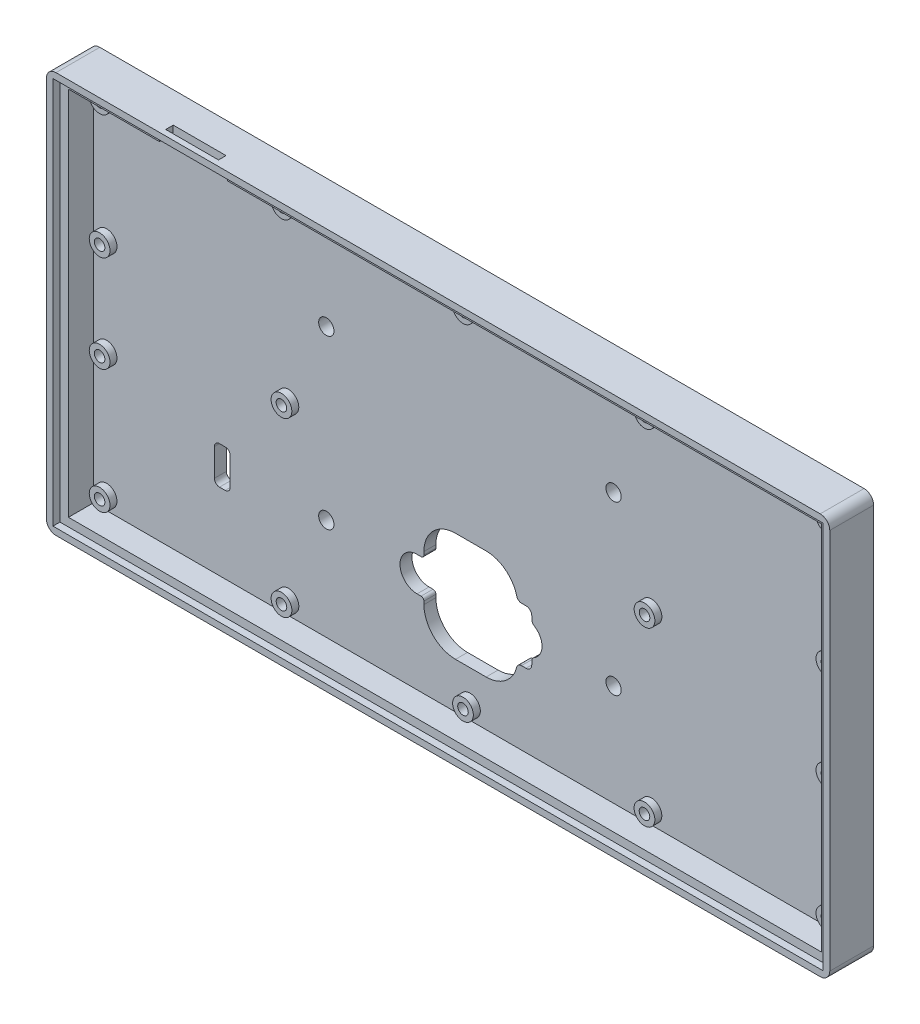
SolidWorks part; units mm, degrees
ref_plane "Front Plane" through (0, 0, 0) normal (0, 0, 1) x (1, 0, 0)
ref_plane "Top Plane" through (0, 0, 0) normal (0, 1, 0) x (1, 0, 0)
ref_plane "Right Plane" through (0, 0, 0) normal (1, 0, 0) x (0, 0, -1)
sketch "PCB" plane through (0, 0, 0) normal (0, 0, 1) x (1, 0, 0)
  line L0 (96.2635, 45.5524) -> (101.8921, 45.5524) construction
  line L1 (-101.8921, 51.181) -> (101.8921, 51.181) construction
  line L2 (-101.8921, 51.181) -> (-101.8921, -51.181) construction
  line L3 (-101.8921, -51.181) -> (101.8921, -51.181) construction
  line L4 (101.8921, 51.181) -> (101.8921, -51.181) construction
  line L5 (-101.8921, 51.181) -> (101.8921, -51.181) construction
  line L6 (-101.8921, -51.181) -> (101.8921, 51.181) construction
  line L7 (96.2635, 45.5524) -> (96.2635, 51.181) construction
  line L8 (-96.2635, 45.5524) -> (-101.8921, 45.5524) construction
  line L9 (-96.2635, -45.5524) -> (-96.2635, -51.181) construction
  line L10 (-92.8243, 0) -> (-92.8243, 25.6794) construction
  line L11 (-98.8568, 31.7119) -> (-86.7918, 31.7119)
  line L12 (-98.8568, 31.7119) -> (-98.8568, 19.6469)
  line L13 (-98.8568, 19.6469) -> (-86.7918, 19.6469)
  line L14 (-86.7918, 31.7119) -> (-86.7918, 19.6469)
  line L15 (-98.8568, 31.7119) -> (-86.7918, 19.6469) construction
  line L16 (-98.8568, 19.6469) -> (-86.7918, 31.7119) construction
  line L17 (-98.8568, 6.0325) -> (-86.7918, 6.0325)
  line L18 (-98.8568, 6.0325) -> (-98.8568, -6.0325)
  line L19 (-98.8568, -6.0325) -> (-86.7918, -6.0325)
  line L20 (-86.7918, 6.0325) -> (-86.7918, -6.0325)
  line L21 (-98.8568, 6.0325) -> (-86.7918, -6.0325) construction
  line L22 (-98.8568, -6.0325) -> (-86.7918, 6.0325) construction
  line L23 (-98.8568, -19.6469) -> (-86.7918, -19.6469)
  line L24 (-98.8568, -19.6469) -> (-98.8568, -31.7119)
  line L25 (-98.8568, -31.7119) -> (-86.7918, -31.7119)
  line L26 (-86.7918, -19.6469) -> (-86.7918, -31.7119)
  line L27 (-98.8568, -19.6469) -> (-86.7918, -31.7119) construction
  line L28 (-98.8568, -31.7119) -> (-86.7918, -19.6469) construction
  line L29 (86.7918, 31.7119) -> (98.8568, 31.7119)
  line L30 (86.7918, 31.7119) -> (86.7918, 19.6469)
  line L31 (86.7918, 19.6469) -> (98.8568, 19.6469)
  line L32 (98.8568, 31.7119) -> (98.8568, 19.6469)
  line L33 (86.7918, 31.7119) -> (98.8568, 19.6469) construction
  line L34 (86.7918, 19.6469) -> (98.8568, 31.7119) construction
  line L35 (86.7918, 6.0325) -> (98.8568, 6.0325)
  line L36 (86.7918, 6.0325) -> (86.7918, -6.0325)
  line L37 (86.7918, -6.0325) -> (98.8568, -6.0325)
  line L38 (98.8568, 6.0325) -> (98.8568, -6.0325)
  line L39 (86.7918, 6.0325) -> (98.8568, -6.0325) construction
  line L40 (86.7918, -6.0325) -> (98.8568, 6.0325) construction
  line L41 (86.7918, -19.6469) -> (98.8568, -19.6469)
  line L42 (86.7918, -19.6469) -> (86.7918, -31.7119)
  line L43 (86.7918, -31.7119) -> (98.8568, -31.7119)
  line L44 (98.8568, -19.6469) -> (98.8568, -31.7119)
  line L45 (86.7918, -19.6469) -> (98.8568, -31.7119) construction
  line L46 (86.7918, -31.7119) -> (98.8568, -19.6469) construction
  line L47 (-92.8243, 0) -> (-92.8243, -25.6794) construction
  line L48 (-92.8243, 25.6794) -> (-101.8921, 25.6794) construction
  line L49 (92.8243, 25.6794) -> (101.8921, 25.6794) construction
  line L50 (-3.114, -17.4711) -> (-3.114, -27.7327) construction
  circle A0 centre (-96.2635, 45.5524) radius 0.9995
  circle A1 centre (-96.2635, -45.5524) radius 0.9995
  circle A2 centre (96.2635, -45.5524) radius 0.9995
  circle A3 centre (96.2635, 45.5524) radius 0.9995
  circle A4 centre (-3.114, -17.4711) radius 1.9939
  circle A5 centre (-3.114, -27.7327) radius 1.9939
  point P0 (0, 0)
  point P14 (-92.8243, 25.6794)
  point P23 (-92.8243, 0)
  point P28 (-92.8243, -25.6794)
  point P33 (92.8243, 25.6794)
  point P38 (92.8243, 0)
  point P43 (92.8243, -25.6794)
  point P54 (0.1092, -22.6019)
  point P55 (-7.5006, -22.6019)
  point P60 (-3.114, -22.6019)
  dimension "D4" = 1.999
  dimension "D14" = 3.9878
  dimension "D1" = 203.7842
  dimension "D2" = 102.362
  dimension "D3" = 5.6286
  dimension "D5" = 25.5016
  dimension "D6" = 25.5016
  dimension "D7" = 9.0678
  dimension "D8" = 12.065
  dimension "D9" = 102.0013
  dimension "D10" = 28.5791
  dimension "D11" = 7.6098
  dimension "D12" = 5.1308
  dimension "D13" = 3.2233
sketch "DT_plug" plane through (0, 0, 0) normal (0, 0, 1) x (1, 0, 0)
  line L0 (29.2774, -40.0231) -> (29.2774, -5.0981) construction
  dimension "D1" = 34.925
sketch "display_screen" plane through (0, 0, 0) normal (0, 0, 1) x (1, 0, 0)
  line L1 (-80.3275, 46.3296) -> (83.7565, 46.3296) construction
  line L2 (-80.3275, 46.3296) -> (-80.3275, -50.9016) construction
  line L3 (-80.3275, -50.9016) -> (83.7565, -50.9016) construction
  line L4 (83.7565, 46.3296) -> (83.7565, -50.9016) construction
  line L5 (-78.2955, 44.2976) -> (78.2955, 44.2976) construction
  line L6 (-78.2955, 44.2976) -> (-78.2955, -44.2976) construction
  line L7 (-78.2955, -44.2976) -> (78.2955, -44.2976) construction
  line L8 (78.2955, 44.2976) -> (78.2955, -44.2976) construction
  point P8 (0, 44.2976)
  point P10 (-78.2955, 0)
  dimension "D1" = 164.084
  dimension "D2" = 97.2312
  dimension "D3" = 6.604
  dimension "D4" = 2.032
  dimension "D5" = 2.032
  dimension "D6" = 5.461
ref_plane "back_of_PCB" through (0, 0, -1.8542) normal (0, 0, 1) x (1, 0, 0)
ref_plane "back_PCB_clearance" through (0, 0, -8.4582) normal (0, 0, 1) x (1, 0, 0)
sketch "Sketch4" plane through (0, 0, 0) normal (0, 0, 1) x (1, 0, 0)
  line L0 (-102.1461, 51.4096) -> (-102.1461, 53.1596) construction
  line L1 (-102.1461, 51.4096) -> (102.1461, 51.4096)
  line L2 (-102.1461, 51.4096) -> (-102.1461, -51.4096)
  line L3 (-102.1461, -51.4096) -> (102.1461, -51.4096)
  line L4 (102.1461, 51.4096) -> (102.1461, -51.4096)
  line L5 (-103.8961, 53.1596) -> (103.8961, 53.1596)
  line L6 (-103.8961, 53.1596) -> (-103.8961, -53.1596)
  line L7 (-103.8961, -53.1596) -> (103.8961, -53.1596)
  line L8 (103.8961, 53.1596) -> (103.8961, -53.1596)
  line L9 (-102.1461, 51.4096) -> (-103.8961, 51.4096) construction
  line L10 (102.1461, -51.4096) -> (102.1461, -53.1596) construction
  line L11 (102.1461, -51.4096) -> (103.8961, -51.4096) construction
  line L12 (-101.8921, 51.181) -> (101.8921, 51.181) construction
  line L13 (-101.8921, 51.181) -> (-101.8921, -51.181) construction
  line L14 (101.8921, 51.181) -> (101.8921, -51.181) construction
  line L15 (-101.8921, -51.181) -> (101.8921, -51.181) construction
  dimension "D1" = 1.75
  dimension "D2" = 0.2286
  dimension "D3" = 0.254
  dimension "D4" = 0.254
  dimension "D5" = 0.2286
extrude "Boss-Extrude1" add sketch "Sketch4" against normal up to surface (1.8542 mm away) up to plane "back_of_PCB"
sketch "Sketch5" plane through (0, 0, -1.8542) normal (0, 0, -1) x (-1, 0, 0)
  line L1 (-103.8961, 53.1596) -> (103.8961, 53.1596)
  line L2 (-103.8961, 53.1596) -> (-103.8961, -53.1596)
  line L3 (-103.8961, -53.1596) -> (103.8961, -53.1596)
  line L4 (103.8961, 53.1596) -> (103.8961, -53.1596)
  line L6 (101.8921, 51.181) -> (-101.8921, 51.181) construction
  line L7 (-99.8931, 49.182) -> (99.8931, 49.182)
  line L8 (-99.8931, 49.182) -> (-99.8931, -49.182)
  line L9 (-99.8931, -49.182) -> (99.8931, -49.182)
  line L10 (99.8931, 49.182) -> (99.8931, -49.182)
  line L11 (-99.8931, 49.182) -> (-99.8931, 51.181) construction
  line L12 (-99.8931, 49.182) -> (-101.8921, 49.182) construction
  line L13 (-101.8921, 51.181) -> (-101.8921, -51.181) construction
  line L14 (99.8931, -49.182) -> (101.8921, -49.182) construction
  line L15 (101.8921, 51.181) -> (101.8921, -51.181) construction
  line L16 (99.8931, -49.182) -> (99.8931, -51.181) construction
  line L17 (101.8921, -51.181) -> (-101.8921, -51.181) construction
  dimension "D1" = 1.999
extrude "Boss-Extrude2" add sketch "Sketch5" along normal up to surface (6.604 mm away) up to plane "back_PCB_clearance"
sketch "Sketch6" plane through (0, 0, -8.4582) normal (0, 0, -1) x (-1, 0, 0)
  line L0 (11.7018, -27.8978) -> (11.7018, -28.6979) construction
  line L1 (-103.8961, 53.1596) -> (103.8961, 53.1596)
  line L2 (-103.8961, 53.1596) -> (-103.8961, -53.1596)
  line L3 (-103.8961, -53.1596) -> (103.8961, -53.1596)
  line L4 (103.8961, 53.1596) -> (103.8961, -53.1596)
  line L5 (3.8278, -8.6319) -> (-4.2865, -8.6319) construction
  line L6 (11.7018, -16.5059) -> (11.7018, -17.306) construction
  line L7 (3.8278, -36.5719) -> (-4.2865, -36.5719) construction
  line L11 (12.9718, -18.576) -> (14.0259, -18.576) construction
  line L13 (12.9718, -26.6278) -> (14.0259, -26.6278) construction
  line L15 (-13.6655, -15.9344) -> (-14.8666, -15.9344) construction
  line L16 (-15.8826, -27.4219) -> (-15.8826, -28.2534) construction
  line L17 (-13.6655, -29.2694) -> (-14.8666, -29.2694) construction
  line L18 (-15.8826, -16.9504) -> (-15.8826, -17.782) construction
  line L20 (12.2098, -27.8978) -> (12.2098, -28.6979)
  line L21 (3.8278, -37.0799) -> (-4.2865, -37.0799)
  line L22 (-13.6655, -29.7774) -> (-14.8666, -29.7774)
  line L23 (-16.3906, -27.4219) -> (-16.3906, -28.2534)
  line L24 (-16.3906, -16.9504) -> (-16.3906, -17.782)
  line L25 (-13.6655, -15.4264) -> (-14.8666, -15.4264)
  line L26 (3.8278, -8.1239) -> (-4.2865, -8.1239)
  line L27 (12.2098, -16.5059) -> (12.2098, -17.306)
  line L28 (12.9718, -18.068) -> (14.0259, -18.068)
  line L29 (12.9718, -27.1358) -> (14.0259, -27.1358)
  arc A0 (-16.7989, -19.407) -> (-16.7989, -25.7969) centre (-14.8666, -22.6019) ccw construction
  arc A1 (12.9718, -18.576) -> (11.7018, -17.306) centre (12.9718, -17.306) cw construction
  arc A2 (12.9718, -26.6278) -> (11.7018, -27.8978) centre (12.9718, -27.8978) ccw construction
  arc A3 (14.0259, -26.6278) -> (14.0259, -18.576) centre (14.0259, -22.6019) ccw construction
  arc A4 (11.7018, -28.6979) -> (3.8278, -36.5719) centre (3.8278, -28.6979) cw construction
  arc A5 (11.7018, -16.5059) -> (3.8278, -8.6319) centre (3.8278, -16.5059) ccw construction
  arc A6 (-4.2865, -8.6319) -> (-11.9202, -14.5755) centre (-4.2865, -16.5059) ccw construction
  arc A7 (-11.9202, -14.5755) -> (-13.6655, -15.9344) centre (-13.6655, -14.1342) cw construction
  arc A8 (-4.2865, -36.5719) -> (-11.9202, -30.6283) centre (-4.2865, -28.6979) cw construction
  arc A9 (-11.9202, -30.6283) -> (-13.6655, -29.2694) centre (-13.6655, -31.0697) ccw construction
  arc A10 (-14.8666, -15.9344) -> (-15.8826, -16.9504) centre (-14.8666, -16.9504) ccw construction
  arc A11 (-15.8826, -17.782) -> (-16.7989, -19.407) centre (-17.7817, -17.782) cw construction
  arc A12 (-15.8826, -27.4219) -> (-16.7989, -25.7969) centre (-17.7817, -27.4219) ccw construction
  arc A13 (-15.8826, -28.2534) -> (-14.8666, -29.2694) centre (-14.8666, -28.2534) ccw construction
  arc A14 (12.2098, -28.6979) -> (3.8278, -37.0799) centre (3.8278, -28.6979) cw
  arc A15 (-4.2865, -37.0799) -> (-12.4127, -30.7529) centre (-4.2865, -28.6979) cw
  arc A16 (-12.4127, -30.7529) -> (-13.6655, -29.7774) centre (-13.6655, -31.0697) ccw
  arc A17 (-16.3906, -28.2534) -> (-14.8666, -29.7774) centre (-14.8666, -28.2534) ccw
  arc A18 (-16.3906, -27.4219) -> (-17.0618, -26.2315) centre (-17.7817, -27.4219) ccw
  arc A19 (-17.0618, -18.9723) -> (-17.0618, -26.2315) centre (-14.8666, -22.6019) ccw
  arc A20 (-16.3906, -17.782) -> (-17.0618, -18.9723) centre (-17.7817, -17.782) cw
  arc A21 (-14.8666, -15.4264) -> (-16.3906, -16.9504) centre (-14.8666, -16.9504) ccw
  arc A22 (-12.4127, -14.451) -> (-13.6655, -15.4264) centre (-13.6655, -14.1342) cw
  arc A23 (-4.2865, -8.1239) -> (-12.4127, -14.451) centre (-4.2865, -16.5059) ccw
  arc A24 (12.2098, -16.5059) -> (3.8278, -8.1239) centre (3.8278, -16.5059) ccw
  arc A25 (12.9718, -18.068) -> (12.2098, -17.306) centre (12.9718, -17.306) cw
  arc A26 (14.0259, -27.1358) -> (14.0259, -18.068) centre (14.0259, -22.6019) ccw
  arc A27 (12.9718, -27.1358) -> (12.2098, -27.8978) centre (12.9718, -27.8978) ccw
  point P6 (-0.1092, -22.6019)
  dimension "D7" = 3.7338
  dimension "D9" = 1.27
  dimension "D3" = 1.0541
  dimension "D10" = 7.874
  dimension "D13" = 1.8002
  dimension "D16" = 1.016
  dimension "D17" = 1.8991
  dimension "D2" = 11.811
  dimension "D4" = 13.97
  dimension "D5" = 15.7734
  dimension "D6" = 6.6675
  dimension "D8" = 1.016
  dimension "D11" = 0.8001
  dimension "D12" = 13.97
  dimension "D14" = 8.1143
  dimension "D15" = 6.6675
  dimension "D22" = 0.508
extrude "Boss-Extrude3" add sketch "Sketch6" along normal blind 3.175
sketch "Sketch10" plane through (0, 0, -11.6332) normal (0, 0, -1) x (-1, 0, 0)
  line L0 (-38.1, 22.225) -> (38.1, 22.225) construction
  line L1 (38.1, 22.225) -> (38.1, -22.225) construction
  line L3 (38.1, 22.225) -> (38.1, 53.1596) construction
  line L4 (-103.8961, 53.1596) -> (103.8961, 53.1596) construction
  line L5 (38.1, -22.225) -> (38.1, -53.1596) construction
  line L6 (103.8961, -53.1596) -> (-103.8961, -53.1596) construction
  circle A0 centre (-38.1, 22.225) radius 2.032
  circle A1 centre (-38.1, 22.225) radius 5.207 construction
  circle A2 centre (-38.1, -22.225) radius 5.207 construction
  circle A3 centre (-38.1, -22.225) radius 2.032
  circle A4 centre (38.1, -22.225) radius 2.032
  circle A5 centre (38.1, -22.225) radius 5.207 construction
  circle A6 centre (38.1, 22.225) radius 2.032
  circle A7 centre (38.1, 22.225) radius 5.207 construction
  point P12 (0, 22.225)
  dimension "D1" = 4.064
  dimension "D2" = 3.175
  dimension "D3" = 76.2
  dimension "D4" = 44.45
extrude "Cut-Extrude1" cut sketch "Sketch10" against normal up to next
fillet "Fillet1" radius 2.54 4 edges at (103.8961, 53.1596, -5.8166) (103.8961, -53.1596, -5.8166) (-103.8961, -53.1596, -5.8166) (-103.8961, 53.1596, -5.8166)
sketch "Sketch11" plane through (0, 0, -8.4582) normal (0, 0, 1) x (1, 0, 0)
  line L0 (-96.3835, 45.671) -> (-96.3835, 51.4096) construction
  line L1 (-96.3835, 45.671) -> (96.3835, 45.671) construction
  line L2 (-96.3835, 45.671) -> (-96.3835, -45.671) construction
  line L3 (-96.3835, -45.671) -> (96.3835, -45.671) construction
  line L4 (96.3835, 45.671) -> (96.3835, -45.671) construction
  line L5 (-102.1461, 51.4096) -> (102.1461, 51.4096) construction
  line L6 (-96.3835, 45.671) -> (-102.1461, 45.671) construction
  line L7 (-102.1461, 51.4096) -> (-102.1461, -51.4096) construction
  line L8 (96.3835, -45.671) -> (102.1461, -45.671) construction
  line L9 (102.1461, -51.4096) -> (102.1461, 51.4096) construction
  line L10 (96.3835, -45.671) -> (96.3835, -51.4096) construction
  line L11 (102.1461, -51.4096) -> (-102.1461, -51.4096) construction
  circle A0 centre (-96.3835, 45.671) radius 1.4
  circle A1 centre (0, 45.671) radius 1.4
  circle A2 centre (96.3835, 45.671) radius 1.4
  circle A3 centre (-96.3835, -45.671) radius 1.4
  circle A4 centre (96.3835, -45.671) radius 1.4
  circle A5 centre (96.3835, -12.808) radius 1.4
  circle A6 centre (96.3835, 12.808) radius 1.4
  circle A7 centre (0, -45.671) radius 1.4
  circle A8 centre (-96.3835, -12.808) radius 1.4
  circle A9 centre (-96.3835, 12.808) radius 1.4
  circle A10 centre (-48.1435, 45.671) radius 1.4
  circle A11 centre (48.1435, 45.671) radius 1.4
  circle A12 centre (48.1435, -45.671) radius 1.4
  circle A13 centre (-48.1435, -45.671) radius 1.4
  circle A14 centre (-48.1545, 0.033) radius 1.4
  circle A15 centre (48.1545, 0.033) radius 1.4
  dimension "D3" = 2.8
  dimension "D1" = 91.342
  dimension "D2" = 192.767
  dimension "D4" = 48.24
  dimension "D5" = 48.24
  dimension "D6" = 32.863
  dimension "D7" = 32.863
  dimension "D8" = 48.229
  dimension "D9" = 45.638
  dimension "D10" = 48.229
  dimension "D11" = 45.638
extrude "Cut-Extrude2" cut sketch "Sketch11" against normal up to next
sketch "Sketch12" plane through (0, 53.1596, 0) normal (0, 1, 0) x (1, 0, 0)
  line L0 (101.3561, 0) -> (-101.3561, 0) construction
  line L1 (-73.7461, 3.5) -> (-59.7461, 3.5)
  line L2 (-73.7461, 3.5) -> (-73.7461, 1.5)
  line L3 (-73.7461, 1.5) -> (-59.7461, 1.5)
  line L4 (-59.7461, 3.5) -> (-59.7461, 1.5)
  line L6 (-103.8961, 0) -> (-103.8961, 11.6332) construction
  dimension "D1" = 1.5
  dimension "D2" = 14
  dimension "D3" = 30.15
  dimension "D4" = 2
extrude "Cut-Extrude3" cut sketch "Sketch12" against normal up to next
sketch "Sketch13" plane through (0, 0, -1.8542) normal (0, 0, 1) x (1, 0, 0)
  line L0 (-59.7461, 51.4096) -> (102.1461, 51.4096) construction
  line L1 (-75.7461, 49.182) -> (-57.7461, 49.182)
  line L2 (-75.7461, 49.182) -> (-75.7461, 51.4096)
  line L3 (-75.7461, 51.4096) -> (-57.7461, 51.4096)
  line L4 (-57.7461, 49.182) -> (-57.7461, 51.4096)
  line L5 (99.8931, 49.182) -> (-99.8931, 49.182) construction
  line L6 (-73.7461, 51.4096) -> (-73.7461, 49.182) construction
  line L7 (-59.7461, 49.182) -> (-59.7461, 53.1596) construction
  dimension "D1" = 2
  dimension "D2" = 2
extrude "Cut-Extrude4" cut sketch "Sketch13" against normal up to surface (1.6458 mm away) up to face at (-66.7461, 51.1708, -3.5)
sketch "Sketch14" plane through (0, 0, -8.4582) normal (0, 0, 1) x (1, 0, 0)
  circle A0 centre (-96.3835, 45.671) radius 1.4
  circle A1 centre (-96.3835, 45.671) radius 2.75
  circle A3 centre (-96.3835, 45.671) radius 1.4 construction
  circle A4 centre (-48.1435, 45.671) radius 2.75
  circle A5 centre (-48.1435, 45.671) radius 1.4
  circle A6 centre (0, 45.671) radius 1.4
  circle A7 centre (0, 45.671) radius 2.75
  circle A8 centre (48.1435, 45.671) radius 1.4
  circle A9 centre (48.1435, 45.671) radius 2.75
  circle A10 centre (96.3835, 45.671) radius 1.4
  circle A11 centre (96.3835, 45.671) radius 2.75
  circle A12 centre (-96.3835, 12.808) radius 1.4
  circle A13 centre (-96.3835, 12.808) radius 2.75
  circle A14 centre (-48.1545, 0.033) radius 1.4
  circle A15 centre (-48.1545, 0.033) radius 2.75
  circle A16 centre (-96.3835, -12.808) radius 1.4
  circle A17 centre (-96.3835, -12.808) radius 2.75
  circle A18 centre (-96.3835, -45.671) radius 1.4
  circle A19 centre (-96.3835, -45.671) radius 2.75
  circle A20 centre (-48.1435, -45.671) radius 1.4
  circle A21 centre (-48.1435, -45.671) radius 2.75
  circle A22 centre (0, -45.671) radius 1.4
  circle A23 centre (0, -45.671) radius 2.75
  circle A24 centre (48.1545, 0.033) radius 1.4
  circle A25 centre (48.1545, 0.033) radius 2.75
  circle A26 centre (48.1435, -45.671) radius 1.4
  circle A27 centre (48.1435, -45.671) radius 2.75
  circle A28 centre (96.3835, -45.671) radius 1.4
  circle A29 centre (96.3835, -45.671) radius 2.75
  circle A30 centre (96.3835, -12.808) radius 1.4
  circle A31 centre (96.3835, -12.808) radius 2.75
  circle A32 centre (96.3835, 12.808) radius 1.4
  circle A33 centre (96.3835, 12.808) radius 2.75
  circle A34 centre (-48.1435, 45.671) radius 1.4 construction
  circle A35 centre (0, 45.671) radius 1.4 construction
  circle A36 centre (48.1435, 45.671) radius 1.4 construction
  circle A37 centre (96.3835, 45.671) radius 1.4 construction
  circle A38 centre (96.3835, 12.808) radius 1.4 construction
  circle A39 centre (48.1545, 0.033) radius 1.4 construction
  circle A40 centre (-48.1545, 0.033) radius 1.4 construction
  circle A41 centre (-96.3835, 12.808) radius 1.4 construction
  circle A42 centre (-96.3835, -12.808) radius 1.4 construction
  circle A43 centre (-96.3835, -45.671) radius 1.4 construction
  circle A44 centre (-48.1435, -45.671) radius 1.4 construction
  circle A45 centre (0, -45.671) radius 1.4 construction
  circle A46 centre (48.1435, -45.671) radius 1.4 construction
  circle A47 centre (96.3835, -45.671) radius 1.4 construction
  circle A48 centre (96.3835, -12.808) radius 1.4 construction
  dimension "D1" = 5.5
extrude "Boss-Extrude4" add sketch "Sketch14" along normal blind 1.85
sketch "Sketch15" plane through (0, 0, -8.4582) normal (0, 0, 1) x (1, 0, 0)
  line L0 (-99.8931, 49.182) -> (-99.8931, -49.182) construction
  line L1 (-66.4371, -18.827) -> (-64.9371, -18.827)
  line L2 (-67.7871, -20.177) -> (-67.7871, -27.477)
  line L3 (-66.4371, -28.827) -> (-64.9371, -28.827)
  line L4 (-63.5871, -20.177) -> (-63.5871, -27.477)
  line L5 (-99.8931, -49.182) -> (99.8931, -49.182) construction
  arc A0 (-64.9371, -28.827) -> (-63.5871, -27.477) centre (-64.9371, -27.477) ccw
  arc A1 (-67.7871, -27.477) -> (-66.4371, -28.827) centre (-66.4371, -27.477) ccw
  arc A2 (-66.4371, -18.827) -> (-67.7871, -20.177) centre (-66.4371, -20.177) ccw
  arc A3 (-64.9371, -18.827) -> (-63.5871, -20.177) centre (-64.9371, -20.177) cw
  point P10 (-63.5871, -28.827)
  point P13 (-67.7871, -28.827)
  point P16 (-67.7871, -18.827)
  dimension "D5" = 1.35
  dimension "D1" = 32.106
  dimension "D2" = 4.2
  dimension "D3" = 10
  dimension "D4" = 20.355
extrude "Cut-Extrude5" cut sketch "Sketch15" against normal up to next
